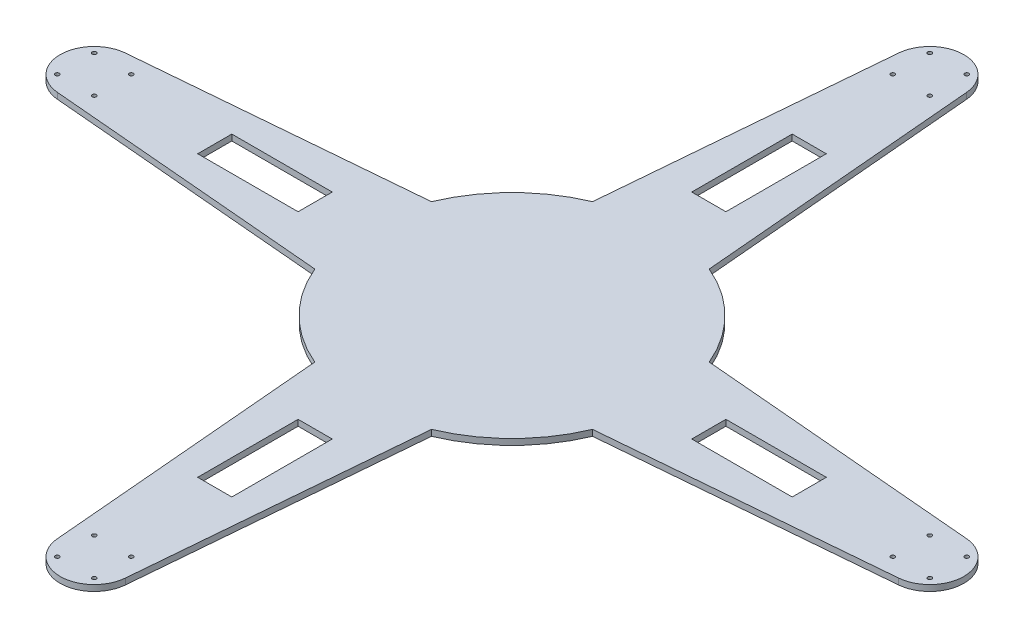
SolidWorks part; units mm, degrees
ref_plane "Front Plane" through (0, 0, 0) normal (0, 0, 1) x (1, 0, 0)
ref_plane "Top Plane" through (0, 0, 0) normal (0, 1, 0) x (1, 0, 0)
ref_plane "Right Plane" through (0, 0, 0) normal (1, 0, 0) x (0, 0, -1)
sketch "Sketch1" plane through (0, 0, 0) normal (0, 1, 0) x (1, 0, 0)
  line L0 (0, 0) -> (151.4608, 13.0629)
  line L1 (151.4608, 46.9371) -> (150, 30) construction
  line L2 (151.4608, 46.9371) -> (0, 60)
  line L4 (150, 30) -> (151.4608, 13.0629) construction
  line L5 (150, 30) -> (0, 30) construction
  line L6 (140.8076, 39.1924) -> (159.1924, 39.1924) construction
  line L7 (159.1924, 39.1924) -> (159.1924, 20.8076) construction
  line L8 (159.1924, 20.8076) -> (140.8076, 20.8076) construction
  line L9 (140.8076, 20.8076) -> (140.8076, 39.1924) construction
  line L10 (140.8076, 39.1924) -> (159.1924, 20.8076) construction
  line L11 (140.8076, 20.8076) -> (159.1924, 39.1924) construction
  line L13 (0, 60) -> (0, 0)
  arc A0 (151.4608, 46.9371) -> (151.4608, 13.0629) centre (150, 30) cw
  circle A1 centre (140.8076, 39.1924) radius 1
  circle A2 centre (140.8076, 20.8076) radius 1
  circle A3 centre (159.1924, 20.8076) radius 1
  circle A4 centre (159.1924, 39.1924) radius 1
  point P0 (0, 0)
  point P13 (150, 30)
  point P15 (0, 0)
  dimension "D1" = 150
  dimension "D3" = 17
  dimension "D5" = 2
  dimension "D2" = 60
  dimension "D4" = 26
  dimension "D6" = 45
extrude "Boss-Extrude1" add sketch "Sketch1" along normal blind 3
sketch "Sketch2" plane through (0, 3, 0) normal (0, 1, 0) x (1, 0, 0)
  line L0 (40, 30) -> (0, 30) construction
  line L1 (40, 38.5) -> (90, 38.5)
  line L2 (40, 38.5) -> (40, 21.5)
  line L3 (40, 21.5) -> (90, 21.5)
  line L4 (90, 38.5) -> (90, 21.5)
  line L5 (0, 60) -> (0, 0) construction
  dimension "D1" = 17
  dimension "D2" = 50
  dimension "D3" = 40
extrude "Cut-Extrude1" cut sketch "Sketch2" against normal through all
sketch "Sketch3" plane through (0, 3, 0) normal (0, 1, 0) x (1, 0, 0)
  line L0 (40, 30) -> (-58, 30) construction
  line L1 (40, 38.5) -> (40, 21.5) construction
  circle A0 centre (-58, 30) radius 75
  arc A2 (151.4608, 13.0629) -> (151.4608, 46.9371) centre (150, 30) ccw construction
  point P10 (167, 30)
  dimension "D1" = 150
  dimension "D2" = 225
extrude "Boss-Extrude2" add sketch "Sketch3" against normal up to surface (3 mm away) up to face at (65, 0, -30)
pattern_circular "CirPattern1" count 4 over 360 about axis through (-58, -212.132, -30) along (0, 1, 0) of "Boss-Extrude1", "Cut-Extrude1"
equation "\"D2@Sketch3\"=450/2"
